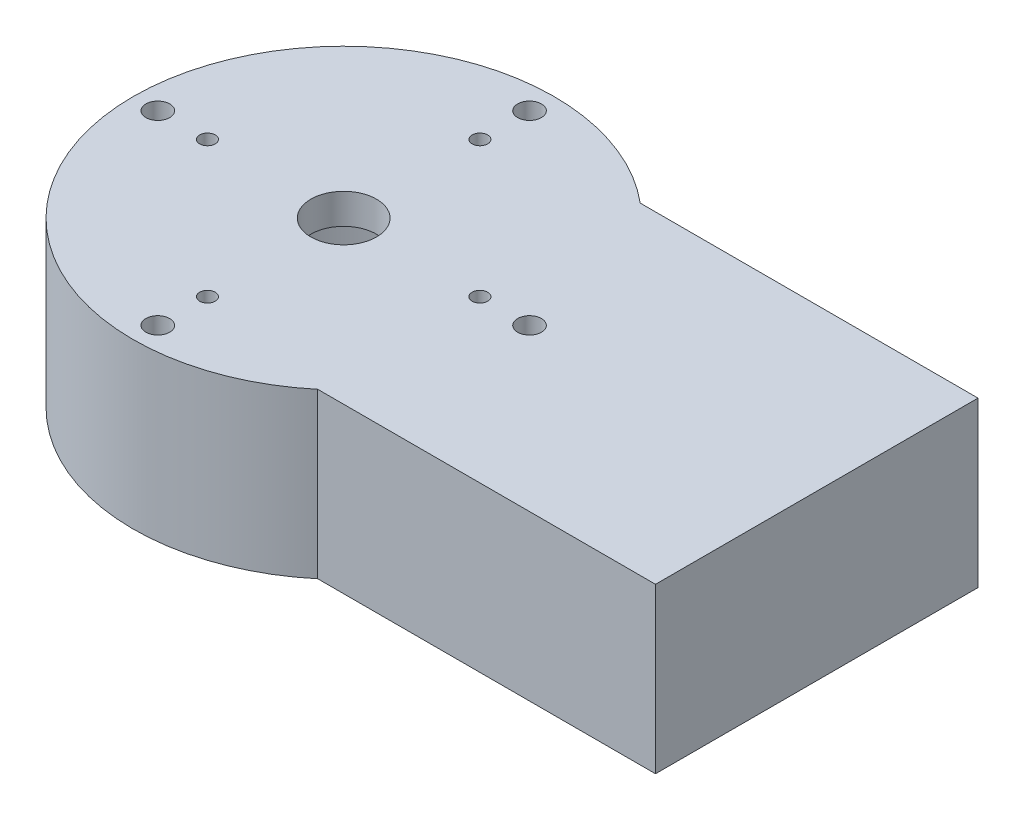
SolidWorks part; units mm, degrees
ref_plane "Front Plane" through (0, 0, 0) normal (0, 0, 1) x (1, 0, 0)
ref_plane "Top Plane" through (0, 0, 0) normal (0, 1, 0) x (1, 0, 0)
ref_plane "Right Plane" through (0, 0, 0) normal (1, 0, 0) x (0, 0, -1)
sketch "Sketch1" plane through (0, 0, 0) normal (0, 1, 0) x (1, 0, 0)
  line L0 (25.65, 0) -> (66.15, 0) construction
  line L1 (66.15, -10.195) -> (106.31, -10.195)
  line L2 (66.15, 10.195) -> (106.31, 10.195)
  line L3 (66.15, 10.195) -> (66.15, -10.195)
  line L4 (66.15, 0) -> (106.31, 0) construction
  line L5 (106.31, 10.195) -> (106.31, -10.195)
  line L6 (114.81, 17.8861) -> (114.81, -17.8861)
  line L7 (57.65, -18.695) -> (113.9869, -18.695)
  line L8 (57.65, 18.695) -> (57.65, -18.695)
  line L9 (57.65, 18.695) -> (113.9869, 18.695)
  line L10 (0, 25.65) -> (96.425, 25.65)
  line L11 (0, -25.65) -> (96.425, -25.65)
  line L12 (57.65, 18.695) -> (114.81, 18.695) construction
  line L13 (114.81, 18.695) -> (114.81, -18.695) construction
  line L14 (57.65, -18.695) -> (114.81, -18.695) construction
  circle A0 centre (0, 0) radius 15.65 construction
  circle A1 centre (16.6, 0) radius 0.95
  circle A2 centre (0, -16.6) radius 0.95
  circle A3 centre (-16.6, 0) radius 0.95
  circle A4 centre (0, 16.6) radius 0.95
  circle A5 centre (0, 0) radius 19.65
  circle A6 centre (0, 0) radius 4
  circle A7 centre (0, 0) radius 25.65
  circle A8 centre (96.425, 0) radius 25.65 construction
  arc A9 (96.425, 25.65) -> (96.425, -25.65) centre (96.425, 0) cw
  arc A10 (0, -25.65) -> (0, 25.65) centre (0, 0) cw
  point P14 (0, 0)
  point P28 (86.23, 0)
  point P29 (96.425, 0)
  dimension "D1" = 31.3
  dimension "D2" = 1.9
  dimension "D5" = 8
  dimension "D7" = 32
  dimension "D8" = 40.16
  dimension "D9" = 20.39
  dimension "D11" = 10.195
  dimension "D4" = 4
  dimension "D6" = 6
  dimension "D10" = 8.5
  dimension "D3" = 4
extrude "Boss-Extrude2" add sketch "Sketch1" along normal blind 3.7 contours A7 A5 | A5 A6 A1 A2 A3 A4 | A9 L10 A7 L11 L7 L8 L9 | A9 L9 L8 L7 L6 L2 L5 L1 L3 | L5 L2 L3 L1 | A9 L6 region at (86.23, 0, 0) region at (117.7544, 0, 0) region at (114.127, 0, 0) region at (50.4952, 0, 0) region at (17.6243, 0, -17.6243) region at (-19.0942, 0, 0)
sketch "Sketch5" plane through (0, 3.7, 0) normal (0, 1, 0) x (1, 0, 0)
  line L0 (57.65, -18.695) -> (113.9869, -18.695) construction
  line L1 (57.65, 18.695) -> (57.65, -18.695) construction
  line L2 (96.425, 25.65) -> (0, 25.65)
  line L3 (0, -25.65) -> (96.425, -25.65)
  line L4 (66.15, -10.195) -> (106.31, -10.195)
  line L5 (106.31, -10.195) -> (106.31, 10.195)
  line L6 (106.31, 10.195) -> (66.15, 10.195)
  line L7 (66.15, 10.195) -> (66.15, -10.195)
  line L8 (66.15, -10.195) -> (106.31, -10.195)
  line L9 (106.31, -10.195) -> (106.31, 10.195)
  line L10 (106.31, 10.195) -> (66.15, 10.195)
  line L11 (66.15, 10.195) -> (66.15, -10.195)
  line L12 (96.425, 25.65) -> (0, 25.65)
  line L13 (0, -25.65) -> (96.425, -25.65)
  line L14 (57.65, 18.695) -> (113.9869, 18.695) construction
  line L15 (114.81, 17.8861) -> (114.81, -17.8861) construction
  line L16 (57.65, -18.695) -> (113.9869, -18.695)
  line L17 (57.65, 18.695) -> (57.65, -18.695)
  line L18 (57.65, 18.695) -> (113.9869, 18.695)
  line L19 (114.81, 17.8861) -> (114.81, -17.8861)
  circle A1 centre (0, 0) radius 4
  circle A2 centre (0, 0) radius 4
  circle A3 centre (0, 0) radius 19.65
  circle A4 centre (0, 0) radius 19.65
  circle A5 centre (0, 16.6) radius 0.95
  circle A6 centre (0, 16.6) radius 0.95
  circle A7 centre (-16.6, 0) radius 0.95
  circle A8 centre (-16.6, 0) radius 0.95
  circle A9 centre (0, -16.6) radius 0.95
  circle A10 centre (0, -16.6) radius 0.95
  circle A11 centre (16.6, 0) radius 0.95
  circle A12 centre (16.6, 0) radius 0.95
  circle A13 centre (0, 0) radius 25.65
  circle A14 centre (0, 0) radius 25.65
  arc A16 (96.425, -25.65) -> (96.425, 25.65) centre (96.425, 0) ccw
  arc A17 (0, 25.65) -> (0, -25.65) centre (0, 0) ccw
  arc A18 (96.425, -25.65) -> (96.425, 25.65) centre (96.425, 0) ccw
  arc A19 (0, 25.65) -> (0, -25.65) centre (0, 0) ccw
  arc M16 (96.425, -25.65) -> (96.425, 25.65) centre (96.425, 0) ccw
  line M17 (96.425, 25.65) -> (0, 25.65)
  arc M18 (0, 25.65) -> (0, -25.65) centre (0, 0) ccw
  line M19 (0, -25.65) -> (96.425, -25.65)
  dimension "D1" = 0
  dimension "D2" = 0
  dimension "D3" = 0
  dimension "D4" = 0
  dimension "D5" = 0
  dimension "D6" = 0
  dimension "D7" = 0
  dimension "D8" = 0
  dimension "D9" = 0
extrude "Boss-Extrude3" add sketch "Sketch5" along normal blind 28.1 contours A14 A4 M18 | L19 L18 L17 L16 L11 L10 L9 L8 M16 | A14 L16 L17 L18 M19 M16 M17 | L19 M16 region at (50.4952, 3.7, 0) region at (17.6243, 3.7, -17.6243) region at (113.9243, 3.7, -17.808) region at (117.7544, 3.7, 0)
sketch "Sketch6" plane through (0, 0, -10.195) normal (0, 0, 1) x (1, 0, 0)
  line L1 (66.15, 31.8) -> (106.31, 31.8)
  line L2 (66.15, 31.8) -> (66.15, 3.7)
  line L3 (66.15, 3.7) -> (106.31, 3.7)
  line L4 (106.31, 31.8) -> (106.31, 3.7)
extrude "Cut-Extrude1" cut sketch "Sketch6" against normal up to next
sketch "Sketch7" plane through (106.31, 0, 0) normal (-1, 0, 0) x (0, 0, 1)
  line L0 (10.195, 3.7) -> (-23.6687, 3.7) construction
  line L1 (-23.6687, 3.7) -> (-23.6687, 31.8) construction
  line L2 (6.195, 3.7) -> (-23.6687, 3.7)
  line L3 (6.195, 3.7) -> (6.195, 13.7)
  line L4 (6.195, 13.7) -> (-23.6687, 13.7)
  line L5 (-23.6687, 3.7) -> (-23.6687, 13.7)
  point P0 (6.195, 3.7)
  dimension "D1" = 4
  dimension "D2" = 10
extrude "Cut-Extrude2" cut sketch "Sketch7" against normal up to next
sketch "Sketch8" plane through (0, 31.8, 0) normal (0, 1, 0) x (1, 0, 0)
  line L0 (57.65, -18.695) -> (113.9869, -18.695) construction
  line L1 (57.65, 18.695) -> (57.65, -18.695) construction
  line L2 (96.425, 25.65) -> (0, 25.65)
  line L3 (0, -25.65) -> (96.425, -25.65)
  line L4 (66.15, -10.195) -> (106.31, -10.195)
  line L5 (106.31, -10.195) -> (106.31, 10.195)
  line L6 (106.31, 10.195) -> (66.15, 10.195)
  line L7 (66.15, 10.195) -> (66.15, -10.195)
  line L8 (66.15, -10.195) -> (106.31, -10.195)
  line L9 (106.31, -10.195) -> (106.31, 10.195)
  line L10 (106.31, 10.195) -> (66.15, 10.195)
  line L11 (66.15, 10.195) -> (66.15, -10.195)
  line L12 (96.425, 25.65) -> (0, 25.65)
  line L13 (0, -25.65) -> (96.425, -25.65)
  line L14 (57.65, 18.695) -> (113.9869, 18.695) construction
  line L15 (114.81, 17.8861) -> (114.81, -17.8861) construction
  line L16 (57.65, -18.695) -> (113.9869, -18.695)
  line L17 (57.65, 18.695) -> (57.65, -18.695)
  line L18 (57.65, 18.695) -> (113.9869, 18.695)
  line L19 (114.81, 17.8861) -> (114.81, -17.8861)
  line L20 (19.65, 0) -> (25.65, 0) construction
  circle A0 centre (22.65, 0) radius 1.45
  circle A1 centre (0, 0) radius 4
  circle A2 centre (0, 0) radius 4
  circle A3 centre (0, 0) radius 19.65
  circle A4 centre (0, 0) radius 19.65
  circle A5 centre (0, 16.6) radius 0.95
  circle A6 centre (0, 16.6) radius 0.95
  circle A7 centre (-16.6, 0) radius 0.95
  circle A8 centre (-16.6, 0) radius 0.95
  circle A9 centre (0, -16.6) radius 0.95
  circle A10 centre (0, -16.6) radius 0.95
  circle A11 centre (16.6, 0) radius 0.95
  circle A12 centre (16.6, 0) radius 0.95
  circle A13 centre (0, 0) radius 25.65
  circle A14 centre (0, 0) radius 25.65
  circle A15 centre (0, -22.65) radius 1.45
  arc A16 (96.425, -25.65) -> (96.425, 25.65) centre (96.425, 0) ccw
  arc A17 (0, 25.65) -> (0, -25.65) centre (0, 0) ccw
  arc A18 (96.425, -25.65) -> (96.425, 25.65) centre (96.425, 0) ccw
  arc A19 (0, 25.65) -> (0, -25.65) centre (0, 0) ccw
  circle A20 centre (-22.65, 0) radius 1.45
  circle A21 centre (0, 22.65) radius 1.45
  point P50 (0, 0)
  dimension "D10" = 2.9
  dimension "D1" = 0
  dimension "D2" = 0
  dimension "D3" = 0
  dimension "D4" = 0
  dimension "D5" = 0
  dimension "D6" = 0
  dimension "D7" = 0
  dimension "D8" = 0
  dimension "D9" = 0
  dimension "D11" = 4
extrude "Cut-Extrude3" cut sketch "Sketch8" against normal through all both and the other way through all contours A20 | A21 | A0 | A15
sketch "Sketch9" plane through (0, 31.8, 0) normal (0, 1, 0) x (1, 0, 0)
  line L0 (57.65, -18.695) -> (113.9869, -18.695) construction
  line L1 (57.65, 18.695) -> (57.65, -18.695) construction
  line L2 (96.425, 25.65) -> (0, 25.65)
  line L3 (0, -25.65) -> (96.425, -25.65)
  line L4 (66.15, -10.195) -> (106.31, -10.195)
  line L5 (106.31, -10.195) -> (106.31, 10.195)
  line L6 (106.31, 10.195) -> (66.15, 10.195)
  line L7 (66.15, 10.195) -> (66.15, -10.195)
  line L8 (66.15, -10.195) -> (106.31, -10.195)
  line L9 (106.31, -10.195) -> (106.31, 10.195)
  line L10 (106.31, 10.195) -> (66.15, 10.195)
  line L11 (66.15, 10.195) -> (66.15, -10.195)
  line L12 (96.425, 25.65) -> (0, 25.65)
  line L13 (0, -25.65) -> (96.425, -25.65)
  line L14 (57.65, 18.695) -> (113.9869, 18.695) construction
  line L15 (114.81, 17.8861) -> (114.81, -17.8861) construction
  line L16 (57.65, -18.695) -> (113.9869, -18.695)
  line L17 (57.65, 18.695) -> (57.65, -18.695)
  line L18 (57.65, 18.695) -> (113.9869, 18.695)
  line L19 (114.81, 17.8861) -> (114.81, -17.8861)
  line L20 (57.65, 0) -> (114.81, 0) construction
  line L21 (85.8184, 18.695) -> (85.8184, -18.695) construction
  circle A0 centre (61.88, -4.95) radius 0.95
  circle A1 centre (0, 0) radius 4
  circle A2 centre (0, 0) radius 4
  circle A3 centre (0, 0) radius 19.65
  circle A4 centre (0, 0) radius 19.65
  circle A5 centre (0, 16.6) radius 0.95
  circle A6 centre (0, 16.6) radius 0.95
  circle A7 centre (-16.6, 0) radius 0.95
  circle A8 centre (-16.6, 0) radius 0.95
  circle A9 centre (0, -16.6) radius 0.95
  circle A10 centre (0, -16.6) radius 0.95
  circle A11 centre (16.6, 0) radius 0.95
  circle A12 centre (16.6, 0) radius 0.95
  circle A13 centre (0, 0) radius 25.65
  circle A14 centre (0, 0) radius 25.65
  circle A15 centre (61.88, 4.95) radius 0.95
  arc A16 (96.425, -25.65) -> (96.425, 25.65) centre (96.425, 0) ccw
  arc A17 (0, 25.65) -> (0, -25.65) centre (0, 0) ccw
  arc A18 (96.425, -25.65) -> (96.425, 25.65) centre (96.425, 0) ccw
  arc A19 (0, 25.65) -> (0, -25.65) centre (0, 0) ccw
  circle A20 centre (109.7569, -4.95) radius 0.95
  circle A21 centre (109.7569, 4.95) radius 0.95
  dimension "D10" = 1.9
  dimension "D11" = 4.27
  dimension "D12" = 4.95
  dimension "D1" = 0
  dimension "D2" = 0
  dimension "D3" = 0
  dimension "D4" = 0
  dimension "D5" = 0
  dimension "D6" = 0
  dimension "D7" = 0
  dimension "D8" = 0
  dimension "D9" = 0
extrude "Cut-Extrude4" cut sketch "Sketch9" against normal blind 12 contours A0 | A15 | A21 | A20
sketch "Sketch12" plane through (0, 31.8, 0) normal (0, 1, 0) x (1, 0, 0)
  line L0 (0, 25.65) -> (96.425, 25.65)
  line L1 (66.15, 25.65) -> (96.425, 25.65) construction
  line L2 (39.15, 19.65) -> (14.5613, 19.65) construction
  line L3 (112.9114, 19.65) -> (16.4864, 19.65)
  line L4 (-11, 0) -> (11, 0) construction
  line L5 (0, -25.65) -> (96.425, -25.65)
  line L6 (112.9114, -19.65) -> (16.4864, -19.65)
  circle A0 centre (0, 0) radius 19.65 construction
  arc A1 (0, 25.65) -> (16.4864, 19.65) centre (0, 0) cw
  arc A2 (121.3157, -6.195) -> (96.425, 25.65) centre (96.425, 0) ccw construction
  arc A3 (96.425, 25.65) -> (112.9114, 19.65) centre (96.425, 0) cw
  arc A4 (96.425, -25.65) -> (112.9114, -19.65) centre (96.425, 0) ccw
  arc A5 (0, -25.65) -> (16.4864, -19.65) centre (0, 0) ccw
extrude "Cut-Extrude5" cut sketch "Sketch12" against normal through all
fillet "Fillet1" radius 2 2 edges at (106.31, 22.75, -19.65) (66.15, 17.75, -19.65)
sketch "Sketch13" plane through (0, 31.8, 0) normal (0, 1, 0) x (1, 0, 0)
  line L0 (57.65, 19.65) -> (57.65, -19.65)
  line L1 (16.4864, 19.65) -> (64.15, 19.65) construction
  line L2 (112.9114, -19.65) -> (16.4864, -19.65) construction
  line L3 (66.15, 17.65) -> (66.15, -10.195) construction
  line L4 (57.65, 19.65) -> (16.4864, 19.65)
  line L5 (16.4864, -19.65) -> (57.65, -19.65)
  arc A0 (16.4864, 19.65) -> (16.4864, -19.65) centre (0, 0) ccw
  dimension "D1" = 8.5
extrude "Cut-Extrude6" cut sketch "Sketch13" against normal blind 11.8
sketch "Sketch14" plane through (0, 20, 0) normal (0, 1, 0) x (1, 0, 0)
  line L0 (57.65, -18.695) -> (113.9869, -18.695) construction
  line L1 (57.65, 18.695) -> (57.65, -18.695) construction
  line L2 (96.425, 25.65) -> (0, 25.65)
  line L3 (0, -25.65) -> (96.425, -25.65)
  line L4 (66.15, -10.195) -> (106.31, -10.195)
  line L5 (106.31, -10.195) -> (106.31, 10.195)
  line L6 (106.31, 10.195) -> (66.15, 10.195)
  line L7 (66.15, 10.195) -> (66.15, -10.195)
  line L8 (66.15, -10.195) -> (106.31, -10.195)
  line L9 (106.31, -10.195) -> (106.31, 10.195)
  line L10 (106.31, 10.195) -> (66.15, 10.195)
  line L11 (66.15, 10.195) -> (66.15, -10.195)
  line L12 (96.425, 25.65) -> (0, 25.65)
  line L13 (0, -25.65) -> (96.425, -25.65)
  line L14 (57.65, 18.695) -> (113.9869, 18.695) construction
  line L15 (114.81, 17.8861) -> (114.81, -17.8861) construction
  line L16 (57.65, -18.695) -> (113.9869, -18.695)
  line L17 (57.65, 18.695) -> (57.65, -18.695)
  line L18 (57.65, 18.695) -> (113.9869, 18.695)
  line L19 (114.81, 17.8861) -> (114.81, -17.8861)
  circle A0 centre (0, 0) radius 19.65
  circle A2 centre (0, 0) radius 4
  circle A3 centre (0, 0) radius 4
  circle A4 centre (0, 0) radius 19.65
  circle A5 centre (0, 0) radius 19.65
  circle A6 centre (0, 16.6) radius 0.95
  circle A7 centre (0, 16.6) radius 0.95
  circle A8 centre (-16.6, 0) radius 0.95
  circle A9 centre (-16.6, 0) radius 0.95
  circle A10 centre (0, -16.6) radius 0.95
  circle A11 centre (0, -16.6) radius 0.95
  circle A12 centre (16.6, 0) radius 0.95
  circle A13 centre (16.6, 0) radius 0.95
  circle A14 centre (0, 0) radius 25.65
  circle A15 centre (0, 0) radius 25.65
  arc A17 (96.425, -25.65) -> (96.425, 25.65) centre (96.425, 0) ccw
  arc A18 (0, 25.65) -> (0, -25.65) centre (0, 0) ccw
  arc A19 (96.425, -25.65) -> (96.425, 25.65) centre (96.425, 0) ccw
  arc A20 (0, 25.65) -> (0, -25.65) centre (0, 0) ccw
  circle M17 centre (0, 0) radius 19.65
  dimension "D1" = 0
  dimension "D2" = 0
  dimension "D3" = 0
  dimension "D4" = 0
  dimension "D5" = 0
  dimension "D6" = 0
  dimension "D7" = 0
  dimension "D8" = 0
  dimension "D9" = 0
extrude "Boss-Extrude4" add sketch "Sketch14" against normal blind 3.7 contours A13 A11 A9 A7 A3 M17 region at (-19.0942, 20, 0)
sketch "Sketch15" plane through (0, 0, 0) normal (0, -1, 0) x (1, 0, 0)
  line L0 (57.65, 18.695) -> (113.9869, 18.695) construction
  line L1 (57.65, -18.695) -> (57.65, 18.695) construction
  line L2 (0, -25.65) -> (96.425, -25.65)
  line L3 (96.425, 25.65) -> (0, 25.65)
  line L4 (106.31, 10.195) -> (66.15, 10.195)
  line L5 (106.31, -10.195) -> (106.31, 10.195)
  line L6 (66.15, -10.195) -> (106.31, -10.195)
  line L7 (66.15, 10.195) -> (66.15, -10.195)
  line L8 (106.31, 10.195) -> (66.15, 10.195)
  line L9 (106.31, -10.195) -> (106.31, 10.195)
  line L10 (66.15, -10.195) -> (106.31, -10.195)
  line L11 (66.15, 10.195) -> (66.15, -10.195)
  line L12 (0, -25.65) -> (96.425, -25.65)
  line L13 (96.425, 25.65) -> (0, 25.65)
  line L14 (57.65, -18.695) -> (113.9869, -18.695) construction
  line L15 (114.81, -17.8861) -> (114.81, 17.8861) construction
  line L16 (57.65, 18.695) -> (113.9869, 18.695)
  line L17 (57.65, -18.695) -> (57.65, 18.695)
  line L18 (57.65, -18.695) -> (113.9869, -18.695)
  line L19 (114.81, -17.8861) -> (114.81, 17.8861)
  circle A0 centre (0, 0) radius 25.65
  circle A2 centre (0, 0) radius 4
  circle A3 centre (0, 0) radius 4
  circle A4 centre (0, 0) radius 19.65
  circle A5 centre (0, 0) radius 19.65
  circle A6 centre (0, -16.6) radius 0.95
  circle A7 centre (0, -16.6) radius 0.95
  circle A8 centre (-16.6, 0) radius 0.95
  circle A9 centre (-16.6, 0) radius 0.95
  circle A10 centre (0, 16.6) radius 0.95
  circle A11 centre (0, 16.6) radius 0.95
  circle A12 centre (16.6, 0) radius 0.95
  circle A13 centre (16.6, 0) radius 0.95
  circle A14 centre (0, 0) radius 25.65
  circle A15 centre (0, 0) radius 25.65
  arc A17 (96.425, -25.65) -> (96.425, 25.65) centre (96.425, 0) ccw
  arc A18 (0, 25.65) -> (0, -25.65) centre (0, 0) ccw
  arc A19 (96.425, -25.65) -> (96.425, 25.65) centre (96.425, 0) ccw
  arc A20 (0, 25.65) -> (0, -25.65) centre (0, 0) ccw
  dimension "D1" = 0
  dimension "D2" = 0
  dimension "D3" = 0
  dimension "D4" = 0
  dimension "D5" = 0
  dimension "D6" = 0
  dimension "D7" = 0
  dimension "D8" = 0
  dimension "D9" = 0
extrude "Cut-Extrude7" cut sketch "Sketch15" against normal up to next contours A5
sketch "Sketch16" plane through (57.65, 0, 0) normal (-1, 0, 0) x (0, 0, 1)
  line L0 (-25.65, 0) -> (25.65, 0) construction
  line L1 (-19.65, 31.8) -> (19.65, 31.8)
  line L2 (-19.65, 31.8) -> (-19.65, 0)
  line L3 (-19.65, 0) -> (19.65, 0)
  line L4 (19.65, 31.8) -> (19.65, 0)
  line L5 (19.65, 20) -> (19.65, 31.8) construction
extrude "Cut-Extrude8" cut sketch "Sketch16" against normal through all
